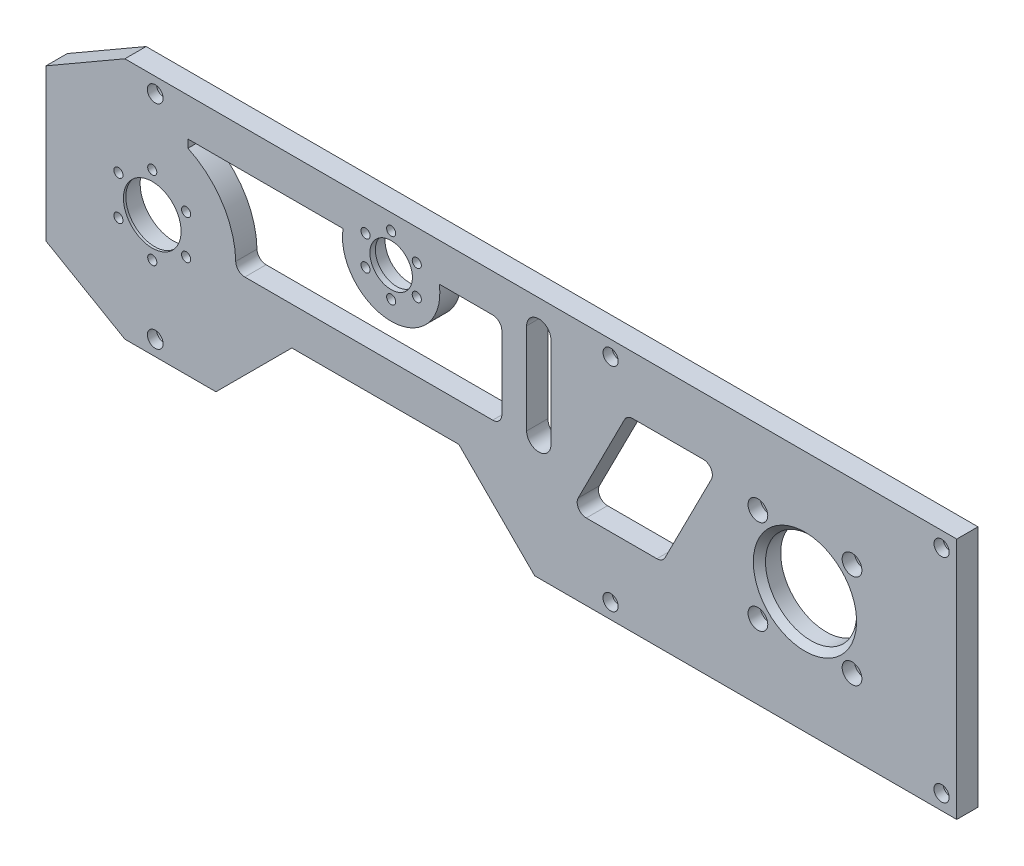
SolidWorks part; units mm, degrees
ref_plane "Front Plane" through (0, 0, 0) normal (0, 0, 1) x (1, 0, 0)
ref_plane "Top Plane" through (0, 0, 0) normal (0, 1, 0) x (1, 0, 0)
ref_plane "Right Plane" through (0, 0, 0) normal (1, 0, 0) x (0, 0, -1)
sketch "Sketch1" plane through (0, 0, 0) normal (0, 0, 1) x (1, 0, 0)
  line L1 (0, 0) -> (300, 0)
  line L2 (0, 0) -> (0, 80)
  line L3 (0, 80) -> (300, 80)
  line L4 (300, 0) -> (300, 80)
  dimension "D1" = 300
  dimension "D2" = 80
extrude "Boss-Extrude1" add sketch "Sketch1" along normal blind 7
chamfer "Chamfer1" distance 15 angle 60 1 edges at (0, 0, 3.5) first distance on face at (0, 40, 3.5)
chamfer "Chamfer3" distance 15 angle 60 1 edges at (0, 80, 3.5) first distance on face at (0, 47.5, 3.5)
sketch "Sketch2" plane through (0, 0, 7) normal (0, 0, 1) x (1, 0, 0)
  line L0 (0, 65) -> (0, 15) construction
  circle A0 centre (35, 40) radius 11
  dimension "D1" = 35
  dimension "D2" = 22
extrude "Cut-Extrude1" cut sketch "Sketch2" against normal blind 10
sketch "Sketch3" plane through (0, 0, 7) normal (0, 0, 1) x (1, 0, 0)
  circle A0 centre (35, 40) radius 9.5
  circle A1 centre (35, 40) radius 11
  dimension "D1" = 19
extrude "Boss-Extrude3" add sketch "Sketch3" against normal blind 0.8
sketch "Sketch4" plane through (0, 0, 7) normal (0, 0, 1) x (1, 0, 0)
  line L0 (162.3249, 70) -> (162.3249, 40) construction
  line L1 (163.3249, 70) -> (163.3249, 40)
  line L2 (161.3249, 70) -> (161.3249, 40)
  line L3 (300, 80) -> (25.9808, 80) construction
  arc A0 (163.3249, 70) -> (161.3249, 70) centre (162.3249, 70) ccw
  arc A1 (161.3249, 40) -> (163.3249, 40) centre (162.3249, 40) ccw
  point P2 (162.3249, 55)
  dimension "D1" = 1
  dimension "D2" = 10
  dimension "D3" = 30
extrude "Cut-Extrude2" cut sketch "Sketch4" against normal through all
sketch "Sketch5" plane through (0, 0, 7) normal (0, 0, 1) x (1, 0, 0)
  line L0 (300, 0) -> (300, 80) construction
  circle A0 centre (250, 40) radius 15
  dimension "D1" = 30
  dimension "D2" = 50
extrude "Cut-Extrude3" cut sketch "Sketch5" against normal through all
sketch "Sketch6" plane through (0, 0, 0) normal (0, 0, -1) x (-1, 0, 0)
  line L0 (-162.3249, 70) -> (-162.3249, 40) construction
  line L1 (-158.3249, 70) -> (-158.3249, 40)
  line L2 (-166.3249, 70) -> (-166.3249, 40)
  arc A0 (-158.3249, 70) -> (-166.3249, 70) centre (-162.3249, 70) ccw
  arc A1 (-166.3249, 40) -> (-158.3249, 40) centre (-162.3249, 40) ccw
  point P4 (-162.3249, 55)
  dimension "D1" = 4
extrude "Cut-Extrude4" cut sketch "Sketch6" against normal blind 8
sketch "Sketch7" plane through (0, 0, 7) normal (0, 0, 1) x (1, 0, 0)
  circle A0 centre (113.6916, 65) radius 8
  dimension "D1" = 16
extrude "Cut-Extrude6" cut sketch "Sketch7" against normal through all
sketch "Sketch8" plane through (0, 0, 7) normal (0, 0, 1) x (1, 0, 0)
  circle A0 centre (113.6916, 65) radius 8
  circle A1 centre (113.6916, 65) radius 7
  dimension "D1" = 14
extrude "Boss-Extrude4" add sketch "Sketch8" against normal blind 1.8
sketch "Sketch9" plane through (0, 0, 0) normal (0, 0, -1) x (-1, 0, 0)
  circle A0 centre (-113.6916, 65) radius 9.75
  circle A1 centre (-113.6916, 74.75) radius 1.5
  circle A2 centre (-105.2479, 69.875) radius 1.5
  circle A3 centre (-105.2479, 60.125) radius 1.5
  circle A4 centre (-113.6916, 55.25) radius 1.5
  circle A5 centre (-122.1354, 60.125) radius 1.5
  circle A6 centre (-122.1354, 69.875) radius 1.5
  point P17 (-113.6916, 65)
  dimension "D1" = 3
  dimension "D2" = 19.5
  dimension "D3" = 6
extrude "Cut-Extrude7" cut sketch "Sketch9" against normal through all contours A1 | A2 | A3 | A4 | A5 | A6
sketch "Sketch10" plane through (0, 0, 0) normal (0, 0, -1) x (-1, 0, 0)
  circle A0 centre (-113.6916, 65) radius 12
  dimension "D1" = 24
extrude "Cut-Extrude8" cut sketch "Sketch10" against normal blind 1
sketch "Sketch11" plane through (0, 0, 0) normal (0, 0, -1) x (-1, 0, 0)
  circle A0 centre (-35, 40) radius 12.875
  circle A1 centre (-35, 52.875) radius 1.5
  circle A2 centre (-23.8499, 46.4375) radius 1.5
  circle A3 centre (-23.8499, 33.5625) radius 1.5
  circle A4 centre (-35, 27.125) radius 1.5
  circle A5 centre (-46.1501, 33.5625) radius 1.5
  circle A6 centre (-46.1501, 46.4375) radius 1.5
  point P17 (-35, 40)
  dimension "D1" = 25.75
  dimension "D2" = 3
  dimension "D3" = 6
extrude "Cut-Extrude9" cut sketch "Sketch11" against normal through all contours A6 | A1 | A2 | A3 | A4 | A5
sketch "Sketch12" plane through (0, 0, 0) normal (0, 0, -1) x (-1, 0, 0)
  line L0 (-300, 80) -> (-25.9808, 80) construction
  line L1 (0, 40) -> (-11.6864, 40) construction
  line L2 (0, 65) -> (0, 15) construction
  line L3 (-300, 0) -> (-300, 80) construction
  circle A0 centre (-35.9808, 75) radius 2.6
  circle A1 centre (-185.9808, 75) radius 2.5
  circle A2 centre (-295, 75) radius 2.5
  circle A3 centre (-35.9808, 5) radius 2.6
  circle A4 centre (-185.9808, 5) radius 2.5
  circle A5 centre (-295, 5) radius 2.5
  dimension "D1" = 5.2
  dimension "D2" = 10
  dimension "D3" = 5
  dimension "D4" = 150
  dimension "D5" = 5
  dimension "D6" = 5
  dimension "D7" = 5
extrude "Cut-Extrude10" cut sketch "Sketch12" against normal through all
sketch "Sketch13" plane through (0, 0, 0) normal (0, 0, -1) x (-1, 0, 0)
  circle A0 centre (-295, 75) radius 4
  circle A1 centre (-185.9808, 75) radius 4
  circle A2 centre (-35.9808, 75) radius 4
  circle A3 centre (-35.9808, 5) radius 4
  circle A4 centre (-185.9808, 5) radius 4
  circle A5 centre (-295, 5) radius 4
  dimension "D1" = 8
  dimension "D2" = 8
  dimension "D3" = 8
  dimension "D4" = 8
  dimension "D5" = 8
  dimension "D6" = 8
extrude "Cut-Extrude11" cut sketch "Sketch13" against normal blind 4
sketch "Sketch14" plane through (0, 0, 7) normal (0, 0, 1) x (1, 0, 0)
  line L1 (234.5, 55.5) -> (265.5, 55.5)
  line L2 (234.5, 55.5) -> (234.5, 24.5)
  line L3 (234.5, 24.5) -> (265.5, 24.5)
  line L4 (265.5, 55.5) -> (265.5, 24.5)
  circle A0 centre (250, 40) radius 15 construction
  circle A1 centre (234.5, 55.5) radius 1.75
  circle A2 centre (265.5, 55.5) radius 1.75
  circle A3 centre (234.5, 24.5) radius 1.75
  circle A4 centre (265.5, 24.5) radius 1.75
  dimension "D5" = 3.5
  dimension "D6" = 3.5
  dimension "D7" = 3.5
  dimension "D8" = 3.5
  dimension "D1" = 31
  dimension "D2" = 31
  dimension "D3" = 15.5
  dimension "D4" = 15.5
extrude "Cut-Extrude12" cut sketch "Sketch14" against normal through all contours A1 | A3 | A4 | A2
sketch "Sketch15" plane through (0, 0, 7) normal (0, 0, 1) x (1, 0, 0)
  line L0 (55.9808, 0) -> (80.9808, 25)
  line L1 (25.9808, 0) -> (300, 0) construction
  line L2 (80.9808, 25) -> (135.9808, 25)
  line L3 (135.9808, 25) -> (160.9808, 0)
  line L4 (55.9808, 0) -> (160.9808, 0)
  dimension "D1" = 55
  dimension "D2" = 30
  dimension "D3" = 25
  dimension "D4" = 45
extrude "Cut-Extrude13" cut sketch "Sketch15" against normal through all
sketch "Sketch16" plane through (0, 0, 7) normal (0, 0, 1) x (1, 0, 0)
  line L0 (173.0745, 25) -> (191.3983, 61)
  line L1 (191.3983, 61) -> (221.3983, 61)
  line L2 (221.3983, 61) -> (203.0745, 25)
  line L3 (203.0745, 25) -> (173.0745, 25)
  line L4 (135.9808, 25) -> (80.9808, 25) construction
  dimension "D1" = 30
  dimension "D2" = 36
extrude "Cut-Extrude14" cut sketch "Sketch16" against normal through all
sketch "Sketch17" plane through (0, 0, 7) normal (0, 0, 1) x (1, 0, 0)
  line L0 (129.5374, 67.5) -> (150.1486, 67.5)
  line L1 (46.7546, 67.5) -> (97.8459, 67.5)
  line L3 (62.3861, 37.5) -> (150.1486, 37.5)
  line L4 (150.1486, 67.5) -> (150.1486, 37.5)
  line L5 (46.7546, 67.5) -> (46.7546, 64.8612)
  arc A0 (62.3861, 37.5) -> (46.7546, 64.8612) centre (35, 40) ccw
  arc A1 (97.8459, 67.5) -> (129.5374, 67.5) centre (113.6916, 65) ccw
  dimension "D1" = 55
  dimension "D2" = 30
extrude "Cut-Extrude15" cut sketch "Sketch17" against normal through all
sketch "Sketch18" plane through (0, 0, 7) normal (0, 0, 1) x (1, 0, 0)
  circle A0 centre (234.5, 55.5) radius 3.25
  arc A1 (236.9621, 57.6214) -> (232.3786, 53.0379) centre (250, 40) ccw
  arc A2 (232.3786, 26.9621) -> (232.3786, 53.0379) centre (250, 40) ccw
  circle A3 centre (265.5, 55.5) radius 3.25
  arc A4 (229.0375, 33.5911) -> (232.3786, 53.0379) centre (250, 40) ccw
  circle A5 centre (265.5, 24.5) radius 3.25
  circle A6 centre (250, 40) radius 21.9203
  circle A7 centre (234.5, 24.5) radius 3.25
  arc A8 (232.3786, 26.9621) -> (263.0379, 57.6214) centre (250, 40) ccw
  point P18 (250, 40)
  dimension "D2" = 6.5
  dimension "D1" = 4
extrude "Cut-Extrude16" cut sketch "Sketch18" against normal blind 4 contours A0 | A3 | A5 | A7
chamfer "Chamfer4" distance 2 angle 45 1 edges at (265, 40, 7)
fillet "Fillet1" radius 3 4 edges at (221.3983, 61, 3.5) (191.3983, 61, 3.5) (203.0745, 25, 3.5) (173.0745, 25, 3.5)
fillet "Fillet2" radius 3 3 edges at (150.1486, 67.5, 3.5) (150.1486, 37.5, 3.5) (62.3861, 37.5, 3.5)
